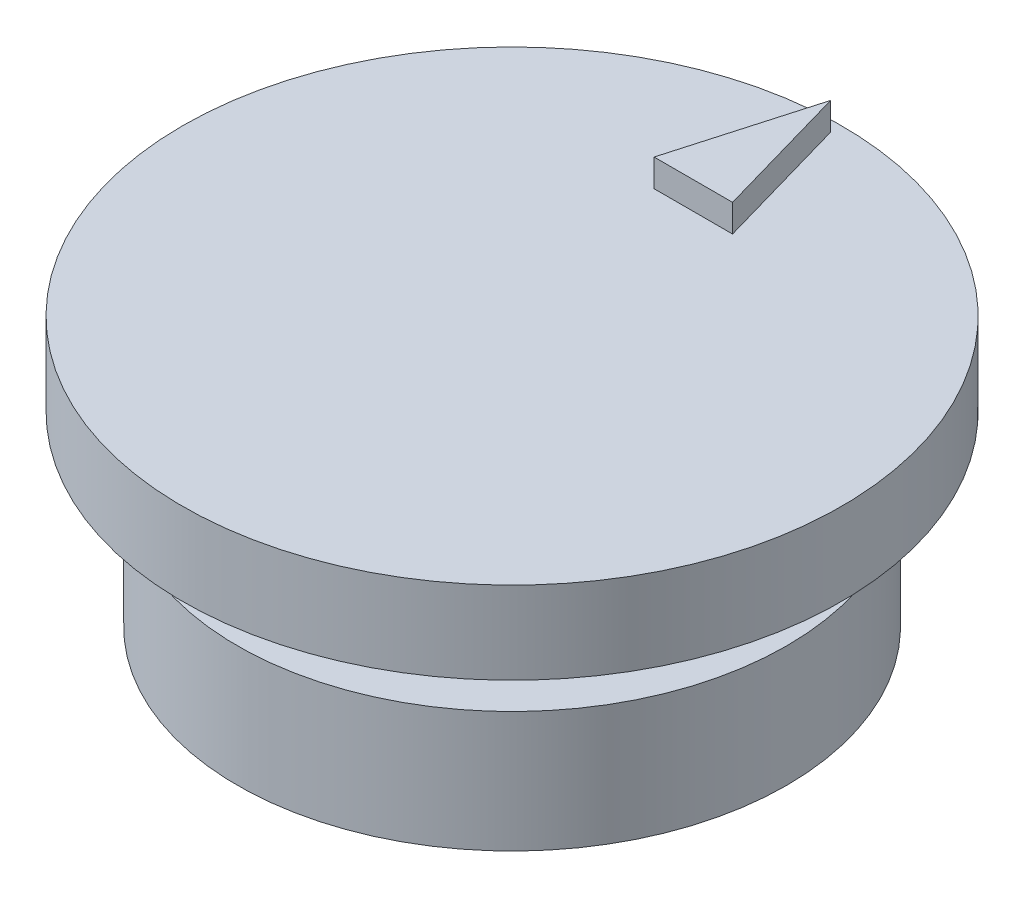
SolidWorks part; units mm, degrees
ref_plane "Front Plane" through (0, 0, 0) normal (0, 0, 1) x (1, 0, 0)
ref_plane "Top Plane" through (0, 0, 0) normal (0, 1, 0) x (1, 0, 0)
ref_plane "Right Plane" through (0, 0, 0) normal (1, 0, 0) x (0, 0, -1)
sketch "Sketch1" plane through (0, 0, 0) normal (0, 0, 1) x (1, 0, 0)
  line L0 (0, -24.4471) -> (0, -36.8931)
  line L1 (0, -36.8931) -> (12.7, -36.8931)
  line L2 (12.7, -36.8931) -> (12.7, -31.3051)
  line L3 (12.7, -31.3051) -> (3.175, -31.3051)
  line L4 (3.175, -31.3051) -> (3.175, -29.7811)
  line L5 (3.175, -29.7811) -> (12.7, -29.7811)
  line L6 (12.7, -29.7811) -> (12.7, -28.2571)
  line L7 (12.7, -28.2571) -> (15.24, -28.2571)
  line L8 (15.24, -28.2571) -> (15.24, -24.4471)
  line L9 (15.24, -24.4471) -> (0, -24.4471)
  dimension "D1" = 3.175
  dimension "D2" = 9.525
  dimension "D3" = 1.524
  dimension "D4" = 5.588
  dimension "D5" = 1.524
  dimension "D6" = 3.81
  dimension "D7" = 12.7
  dimension "D8" = 15.24
revolve "dial base shape" add sketch "Sketch1" angle 360 about L0
sketch "Sketch2" plane through (0, -24.4471, 0) normal (0, 1, 0) x (1, 0, 0)
  line L0 (0, 14.732) -> (-1.8139, 8.382)
  line L1 (-1.8139, 8.382) -> (1.8139, 8.382)
  line L2 (1.8139, 8.382) -> (0, 14.732)
  dimension "D1" = 6.35
  dimension "D2" = 8.382
  dimension "D3" = 6.604
  dimension "D4" = 6.604
extrude "arrow" add sketch "Sketch2" along normal blind 1.27
sketch "Sketch3" plane through (0, -36.8931, 0) normal (0, -1, 0) x (1, 0, 0)
  circle A0 centre (0, -9.8549) radius 1.7989
extrude "flag" add sketch "Sketch3" along normal blind 6.35
